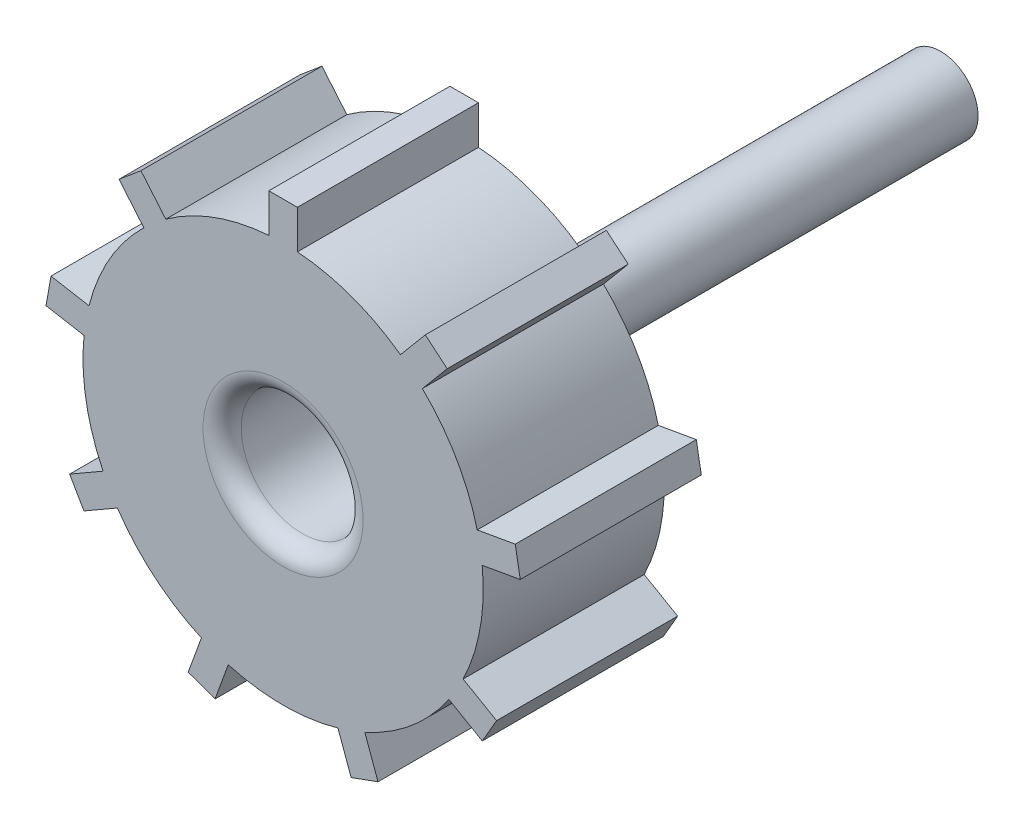
SolidWorks part; units mm, degrees
ref_plane "Ebene vorne" through (0, 0, 0) normal (0, 0, 1) x (1, 0, 0)
ref_plane "Ebene oben" through (0, 0, 0) normal (0, 1, 0) x (1, 0, 0)
ref_plane "Ebene rechts" through (0, 0, 0) normal (1, 0, 0) x (0, 0, -1)
sketch "Skizze1" plane through (0, 0, 0) normal (0, 0, 1) x (1, 0, 0)
  circle A0 centre (0, 0) radius 6
  dimension "D1" = 12
extrude "Aufsatz-Linear austragen1" add sketch "Skizze1" along normal blind 9
sketch "Skizze2" plane through (0, 0, 0) normal (0, 0, -1) x (-1, 0, 0)
  circle A0 centre (0, 0) radius 3.925
  dimension "D1" = 7.85
extrude "Aufsatz-Linear austragen2" add sketch "Skizze2" along normal blind 41
sketch "Skizze3" plane through (0, 0, 9) normal (0, 0, 1) x (1, 0, 0)
  circle A0 centre (0, 0) radius 21
  dimension "D1" = 42
extrude "Aufsatz-Linear austragen3" add sketch "Skizze3" along normal blind 19
sketch "Skizze4" plane through (0, 0, 28) normal (0, 0, 1) x (1, 0, 0)
  circle A0 centre (0, 0) radius 6.4
  dimension "D1" = 12.8
extrude "Schnitt-Linear austragen2" cut sketch "Skizze4" against normal blind 10
fillet "Verrundung1" radius 2 1 edges at (6.4, 0, 28)
sketch "Skizze5" plane through (0, 0, -41) normal (0, 0, -1) x (-1, 0, 0)
  circle A0 centre (0, 0) radius 1.5
  dimension "D1" = 3
extrude "Schnitt-Linear austragen3" cut sketch "Skizze5" against normal blind 15
sketch "Skizze6" plane through (0, 0, 28) normal (0, 0, 1) x (1, 0, 0)
  line L0 (0, 0) -> (0, 21) construction
  line L1 (0, 21) -> (0, 25) construction
  line L2 (-1.5, 25) -> (1.5, 25)
  line L3 (-1.5, 25) -> (-1.5, 20.9464)
  line L4 (1.5, 25) -> (1.5, 20.9464)
  circle A0 centre (0, 0) radius 21
  point P8 (0, 25)
  circle M3 centre (0, 0) radius 8.4
  circle M4 centre (0, 0) radius 21
  dimension "D2" = 42
  dimension "D1" = 4
  dimension "D3" = 3
extrude "Aufsatz-Linear austragen4" add sketch "Skizze6" against normal up to surface (19 mm away) contours L4 L2 L3 M4 | M4 M3 region at (0, 22.991, 28) region at (0, 20.406, 28) up to face at (6, 0, 9)
pattern_circular "Kreismuster1" count 9 over 360 about axis through (0, 0, 28) along (0, 0, -1) of "Aufsatz-Linear austragen4" reverse direction yes
